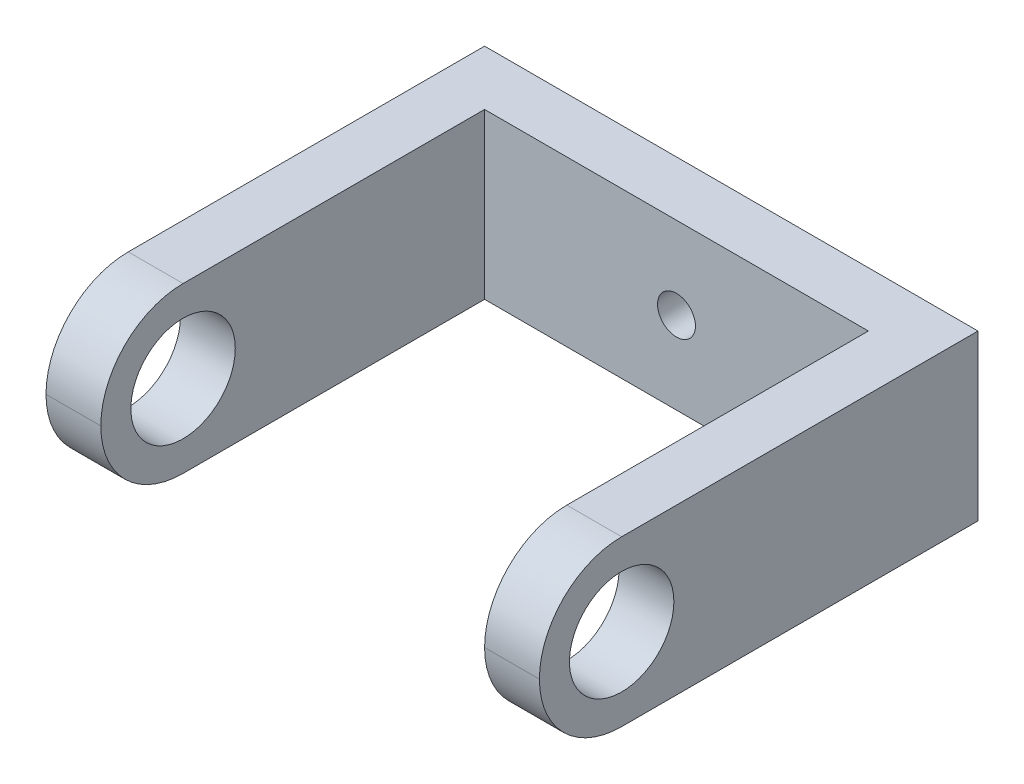
SolidWorks part; units mm, degrees
material "6061 Alloy"
ref_plane "Front Plane" through (0, 0, 0) normal (0, 0, 1) x (1, 0, 0)
ref_plane "Top Plane" through (0, 0, 0) normal (0, 1, 0) x (1, 0, 0)
ref_plane "Right Plane" through (0, 0, 0) normal (1, 0, 0) x (0, 0, -1)
sketch "Sketch1" plane through (0, 0, 0) normal (0, 1, 0) x (1, 0, 0)
  line L0 (-17.5, -7.5) -> (-22.5, -7.5)
  line L1 (-22.5, -7.5) -> (-22.5, 32.5)
  line L3 (-22.5, 32.5) -> (22.5, 32.5)
  line L5 (22.5, 32.5) -> (22.5, -7.5)
  line L6 (22.5, -7.5) -> (17.5, -7.5)
  line L7 (17.5, -7.5) -> (17.5, 27.5)
  line L9 (17.5, 27.5) -> (-17.5, 27.5)
  line L11 (-17.5, 27.5) -> (-17.5, -7.5)
  line L16 (0, 27.5) -> (0, 32.5) construction
  point P5 (0, 27.5)
  dimension "D1" = 5
  dimension "D2" = 35
  dimension "D3" = 27.5
  dimension "D6" = 7.5
extrude "Boss-Extrude1" add sketch "Sketch1" along normal mid plane 15
sketch "Sketch3" plane through (0, 0, 0) normal (1, 0, 0) x (0, 0, -1)
  circle A0 centre (0, 0) radius 4.7625
  dimension "D1" = 9.525
extrude "Cut-Extrude1" cut sketch "Sketch3" against normal through all both and the other way through all
fillet "Fillet1" radius 7.5 4 edges at (20, 7.5, 7.5) (20, -7.5, 7.5) (-20, -7.5, 7.5) (-20, 7.5, 7.5)
hole_wizard "#8-32 Tapped Hole1" positions "Sketch4" profile "Sketch5" tap size "#8-32" standard "ANSI Inch" end condition through all
sketch "Sketch4" plane through (0, 0, -27.5) normal (0, 0, 1) x (1, 0, 0)
  point P0 (0, 0)
sketch "Sketch5" plane through (0, 0, -27.5) normal (1, 0, 0) x (0, -1, 0)
  line L0 (0, 0) -> (0, 5)
  line L1 (0, 5) -> (1.7272, 5)
  line L2 (1.7272, 5) -> (1.7272, 0)
  line L5 (1.7272, 0) -> (0, 0)
  line L11 (0, -6.35) -> (0, 107.95) construction
  dimension "Thru Tap Drill Dia." = 3.4544
  dimension "Thru Tap Drill Depth" = 5
cosmetic thread "Hole Thread1" parameters "D2"=4.1656
